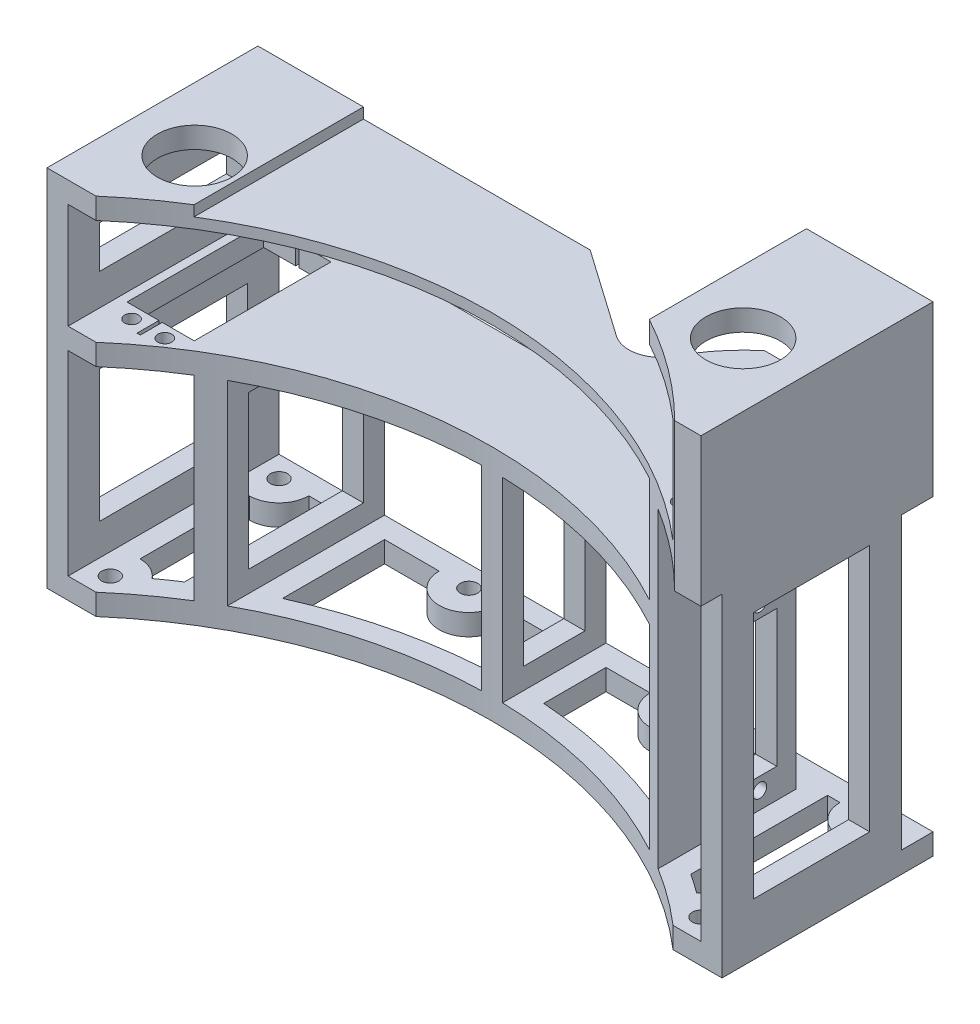
SolidWorks part; units mm, degrees
ref_plane "Front Plane" through (0, 0, 0) normal (0, 0, 1) x (1, 0, 0)
ref_plane "Top Plane" through (0, 0, 0) normal (0, 1, 0) x (1, 0, 0)
ref_plane "Right Plane" through (0, 0, 0) normal (1, 0, 0) x (0, 0, -1)
sketch "Sketch1" plane through (0, 0, 0) normal (0, 0, 1) x (1, 0, 0)
  line L0 (-101.6, 106.425) -> (101.6, 106.425)
  line L1 (-101.6, 0) -> (101.6, 0)
  line L2 (-101.6, 0) -> (-101.6, 106.425)
  line L4 (101.6, 0) -> (101.6, 106.425)
  point P5 (0, 0)
  dimension "D1" = 203.2
  dimension "D2" = 106.425
extrude "Boss-Extrude1" add sketch "Sketch1" along normal mid plane 63.5 contours L1 L4 L0 L2 | L0 region at (0, 53.2125, 0)
sketch "Sketch4" plane through (0, 0, -31.75) normal (0, 0, -1) x (-1, 0, 0)
  line L0 (-101.6, 0) -> (-101.6, 106.425) construction
  line L1 (101.6, 0) -> (101.6, 106.425) construction
  line L2 (-95.25, 103.25) -> (95.25, 103.25)
  line L3 (-95.25, 103.25) -> (-95.25, 71.5)
  line L4 (-95.25, 71.5) -> (95.25, 71.5)
  line L5 (95.25, 103.25) -> (95.25, 71.5)
  line L11 (-95.25, 65.15) -> (95.25, 65.15)
  line L12 (-95.25, 65.15) -> (-95.25, 6.35)
  line L13 (-95.25, 6.35) -> (95.25, 6.35)
  line L14 (95.25, 65.15) -> (95.25, 6.35)
  line L15 (101.6, 0) -> (-101.6, 0) construction
  dimension "D4" = 6.35
  dimension "D1" = 6.35
  dimension "D2" = 71.5
  dimension "D3" = 6.35
  dimension "D5" = 6.35
  dimension "D6" = 31.75
extrude "Cut-Extrude2" cut sketch "Sketch4" against normal through all
sketch "Sketch8" plane through (0, 0, 0) normal (0, 0, 1) x (1, 0, 0)
  line L0 (-95.25, 65.15) -> (95.25, 65.15) construction
  line L1 (-69.85, 65.15) -> (-63.5, 65.15)
  line L2 (-69.85, 65.15) -> (-69.85, 6.35)
  line L3 (-69.85, 6.35) -> (-63.5, 6.35)
  line L4 (-63.5, 65.15) -> (-63.5, 6.35)
  line L5 (95.25, 6.35) -> (-95.25, 6.35) construction
  line L6 (-95.25, 103.25) -> (95.25, 103.25) construction
  line L7 (63.5, 103.25) -> (69.85, 103.25)
  line L8 (63.5, 103.25) -> (63.5, 6.35)
  line L9 (63.5, 6.35) -> (69.85, 6.35)
  line L10 (69.85, 103.25) -> (69.85, 6.35)
  line L11 (95.25, 65.15) -> (95.25, 6.35) construction
  line L12 (-95.25, 6.35) -> (-95.25, 65.15) construction
  line L13 (-101.6, 0) -> (101.6, 0) construction
  line L14 (-3.175, 65.15) -> (3.175, 65.15)
  line L15 (-3.175, 65.15) -> (-3.175, 6.35)
  line L16 (-3.175, 6.35) -> (3.175, 6.35)
  line L17 (3.175, 65.15) -> (3.175, 6.35)
  point P24 (0, 0)
  point P25 (0, 6.35)
  dimension "D1" = 6.35
  dimension "D2" = 6.35
  dimension "D3" = 25.4
  dimension "D4" = 25.4
  dimension "D5" = 6.35
extrude "Boss-Extrude2" add sketch "Sketch8" along normal up to surface (31.75 mm away) from surface up to face at (0, 87.375, 31.75) starting at face at (0, 87.375, -31.75)
sketch "Sketch15" plane through (0, 103.25, 0) normal (0, -1, 0) x (1, 0, 0)
  line L4 (69.85, 31.75) -> (69.85, -31.75)
  line L5 (69.85, -31.75) -> (95.25, -31.75)
  line L6 (95.25, -31.75) -> (95.25, 31.75)
  line L7 (95.25, 31.75) -> (69.85, 31.75)
  line L8 (69.85, 31.75) -> (69.85, -31.75)
  line L9 (69.85, -31.75) -> (95.25, -31.75)
  line L10 (95.25, -31.75) -> (95.25, 31.75)
  line L11 (95.25, 31.75) -> (69.85, 31.75)
  dimension "D1" = 0
extrude "Boss-Extrude4" add sketch "Sketch15" along normal blind 3.175
sketch "Sketch2" plane through (0, 71.5, 0) normal (0, 1, 0) x (1, 0, 0)
  line L0 (-92.677, 24.55) -> (-72.423, -16.604) construction
  line L29 (-92.677, 24.55) -> (-83.05, 24.55)
  line L30 (-92.677, 24.55) -> (-92.677, -16.604)
  line L31 (-92.677, -16.604) -> (-83.05, -16.604)
  line L34 (-72.423, 24.55) -> (-72.423, -16.604)
  line L58 (69.85, 31.75) -> (69.85, -31.75)
  line L59 (69.85, -31.75) -> (95.25, -31.75)
  line L60 (95.25, -31.75) -> (95.25, 31.75)
  line L61 (95.25, 31.75) -> (69.85, 31.75)
  line L62 (69.85, 31.75) -> (69.85, -31.75)
  line L63 (69.85, -31.75) -> (95.25, -31.75)
  line L64 (95.25, -31.75) -> (95.25, 31.75)
  line L65 (95.25, 31.75) -> (69.85, 31.75)
  line L78 (-72.423, 24.55) -> (-92.677, -16.604) construction
  line L79 (-87.55, 28.273) -> (-77.55, -20.327) construction
  line L80 (-87.55, -20.327) -> (-77.55, 28.273) construction
  line L81 (-82.05, -16.604) -> (-72.423, -16.604)
  line L82 (-82.05, -16.604) -> (-82.05, -23.208)
  line L83 (-82.05, -23.208) -> (-83.05, -23.208)
  line L84 (-83.05, -16.604) -> (-83.05, -23.208)
  line L85 (-82.55, 3.973) -> (-13.3966, 3.973) construction
  line L86 (-82.05, 31.154) -> (-83.05, 31.154)
  line L87 (-82.05, 24.55) -> (-82.05, 31.154)
  line L88 (-83.05, 24.55) -> (-83.05, 31.154)
  line L89 (-82.05, 24.55) -> (-72.423, 24.55)
  line L90 (-101.6, -31.75) -> (101.6, -31.75) construction
  line L91 (-101.6, -31.75) -> (-101.6, 31.75) construction
  circle A12 centre (-87.55, -20.327) radius 2.1
  circle A13 centre (-77.55, -20.327) radius 2.1
  circle A14 centre (-87.55, 28.273) radius 2.1
  circle A15 centre (-77.55, 28.273) radius 2.1
  point P8 (-82.55, -23.208)
  point P17 (-82.55, 3.973)
  point P18 (-82.55, 3.973)
  point P27 (-82.55, -6.35)
  dimension "D3" = 48.6
  dimension "D4" = 4.2
  dimension "D2" = 10
  dimension "D5" = 41.154
  dimension "D6" = 20.254
  dimension "D7" = 1
  dimension "D8" = 6.604
  dimension "D9" = 30.9
  dimension "D10" = 25.4
  dimension "D11" = 0
  dimension "D12" = 19.05
extrude "Cut-Extrude3" cut sketch "Sketch2" against normal up to next
sketch "Sketch9" plane through (0, 106.425, 0) normal (0, 1, 0) x (1, 0, 0)
  line L0 (72.423, 24.55) -> (92.677, -16.604) construction
  line L1 (72.423, 24.55) -> (82.05, 24.55)
  line L2 (72.423, 24.55) -> (72.423, -16.604)
  line L3 (72.423, -16.604) -> (82.05, -16.604)
  line L4 (92.677, 24.55) -> (92.677, -16.604)
  line L5 (92.677, 24.55) -> (72.423, -16.604) construction
  line L6 (77.55, 28.273) -> (87.55, -20.327) construction
  line L7 (77.55, -20.327) -> (87.55, 28.273) construction
  line L8 (83.05, -16.604) -> (92.677, -16.604)
  line L9 (83.05, -16.604) -> (83.05, -23.208)
  line L10 (83.05, -23.208) -> (82.05, -23.208)
  line L11 (82.05, -16.604) -> (82.05, -23.208)
  line L12 (82.55, 3.973) -> (164.4034, 3.973) construction
  line L13 (83.05, 31.154) -> (82.05, 31.154)
  line L14 (83.05, 24.55) -> (83.05, 31.154)
  line L15 (82.05, 24.55) -> (82.05, 31.154)
  line L16 (83.05, 24.55) -> (92.677, 24.55)
  line L17 (101.6, -31.75) -> (101.6, 31.75) construction
  line L19 (-101.6, -31.75) -> (101.6, -31.75) construction
  circle A0 centre (77.55, -20.327) radius 2.1
  circle A1 centre (87.55, -20.327) radius 2.1
  circle A2 centre (77.55, 28.273) radius 2.1
  circle A3 centre (87.55, 28.273) radius 2.1
  point P8 (82.55, -23.208)
  point P17 (82.55, 3.973)
  point P18 (82.55, 3.973)
  point P27 (82.55, -6.35)
  dimension "D3" = 4.2
  dimension "D1" = 10
  dimension "D2" = 48.6
  dimension "D4" = 41.154
  dimension "D5" = 20.254
  dimension "D6" = 1
  dimension "D7" = 6.604
  dimension "D8" = 30.9
  dimension "D9" = 19.05
  dimension "D10" = 25.4
extrude "Cut-Extrude4" cut sketch "Sketch9" against normal up to next
sketch "Sketch12" plane through (0, 0, 0) normal (0, 1, 0) x (1, 0, 0)
  line L0 (-63.5, -31.75) -> (-63.5, 31.75) construction
  line L1 (-69.85, -31.75) -> (-95.25, -31.75) construction
  line L2 (-95.25, -31.75) -> (-95.25, 31.75) construction
  line L3 (-101.6, 31.75) -> (101.6, 31.75) construction
  circle A0 centre (-88.9, 25.4) radius 2.6
  circle A1 centre (-88.9, -25.4) radius 2.6
  circle A2 centre (-31.75, 25.4) radius 2.6
  dimension "D1" = 5.2
  dimension "D2" = 6.35
  dimension "D3" = 6.35
  dimension "D4" = 6.35
  dimension "D5" = 31.75
extrude "Cut-Extrude7" cut sketch "Sketch12" along normal up to surface (6.35 mm away) and the other way through all up to face at (-33.3375, 6.35, 0)
mirror "Mirror1" about plane through (0, 0, 0) normal (1, 0, 0) of "Cut-Extrude7"
sketch "Sketch16" plane through (0, 106.425, 0) normal (0, 1, 0) x (1, 0, 0)
  line L2 (-69.85, 31.75) -> (-101.6, 31.75)
  line L3 (-101.6, 31.75) -> (-101.6, -31.75)
  line L12 (-101.6, -31.75) -> (-69.85, -31.75)
  line L13 (-69.85, 31.75) -> (-69.85, -31.75)
  dimension "D1" = 31.75
extrude "Boss-Extrude5" add sketch "Sketch16" along normal blind 3.175
sketch "Sketch17" plane through (0, 109.6, 0) normal (0, 1, 0) x (1, 0, 0)
  line L0 (-101.6, -31.75) -> (-69.85, -31.75) construction
  line L1 (-101.6, 31.75) -> (-101.6, -31.75) construction
  circle A0 centre (-82.55, -6.35) radius 11.2395
  dimension "D3" = 22.479
  dimension "D1" = 25.4
  dimension "D2" = 19.05
extrude "Cut-Extrude8" cut sketch "Sketch17" against normal up to next
sketch "Sketch18" plane through (0, 106.425, 0) normal (0, 1, 0) x (1, 0, 0)
  line L5 (101.6, -31.75) -> (101.6, 31.75) construction
  line L6 (-69.85, -31.75) -> (101.6, -31.75) construction
  line L14 (101.6, -31.75) -> (101.6, 31.75)
  line L15 (101.6, 31.75) -> (95.25, 31.75)
  line L16 (95.25, -31.75) -> (95.25, 31.75)
  line L22 (95.25, -31.75) -> (82.55, -31.75)
  line L23 (101.6, -31.75) -> (101.6, -38.1)
  line L24 (101.6, -38.1) -> (82.55, -38.1)
  line L25 (82.55, -31.75) -> (82.55, -38.1)
  point P4 (0, 0)
  point P5 (95.25, -31.75)
  point P6 (95.25, 30.5966)
  dimension "D4" = 6.35
  dimension "D5" = 19.05
extrude "Boss-Extrude6" add sketch "Sketch18" along normal blind 38.1 from surface starting at face at (87.55, 100.075, 18.227)
sketch "Sketch20" plane through (0, 138.175, 0) normal (0, 1, 0) x (1, 0, 0)
  line L1 (63.5, 31.75) -> (101.6, 31.75)
  line L2 (63.5, 31.75) -> (63.5, -38.1)
  line L3 (63.5, -38.1) -> (101.6, -38.1)
  line L4 (101.6, 31.75) -> (101.6, -38.1)
  line L6 (-69.85, -31.75) -> (82.55, -31.75) construction
  circle A0 centre (82.55, -6.35) radius 11.2395
  point P0 (0, 0)
  dimension "D2" = 19.05
  dimension "D1" = 22.479
  dimension "D4" = 38.1
  dimension "D3" = 25.4
extrude "Boss-Extrude7" add sketch "Sketch20" along normal blind 6.35
sketch "Sketch10" plane through (0, 106.425, 0) normal (0, 1, 0) x (1, 0, 0)
  circle A3 centre (0, -132.08) radius 131.1117 construction
  circle A4 centre (0, -132.08) radius 131.1117 construction
  circle A5 centre (0, -132.08) radius 132.6992
  dimension "D1" = 1.5875
extrude "Cut-Extrude5" cut sketch "Sketch10" against normal through all both and the other way through all
sketch "Sketch21" plane through (0, 106.425, 0) normal (0, 1, 0) x (1, 0, 0)
  line L5 (34.6759, 6.35) -> (-1.5991, 31.75)
  line L6 (-69.85, 31.75) -> (95.25, 31.75) construction
  line L7 (-1.5991, 31.75) -> (50.9018, 31.75)
  arc A1 (34.6759, 6.35) -> (50.9018, 31.75) centre (82.55, -6.35) cw
  point P5 (37.1206, 13.3829)
  dimension "D2" = 49.53
  dimension "D1" = 35
  dimension "D3" = 25.4
extrude "Cut-Extrude10" cut sketch "Sketch21" against normal up to surface (3.175 mm away) up to face at (-82.55, 103.25, 17.5895)
sketch "Sketch32" plane through (0, 6.35, 0) normal (0, 1, 0) x (1, 0, 0)
  line L8 (76.2, 25.4) -> (76.2, -15.769)
  line L9 (88.9, -25.1619) -> (88.9, 25.4)
  line L10 (88.9, 25.4) -> (76.2, 25.4)
  line L11 (76.2, 25.4) -> (76.2, -15.769)
  line L12 (88.9, -16.45) -> (88.9, 16.45)
  line L13 (79.95, 25.4) -> (76.2, 25.4)
  line L32 (-57.15, 25.4) -> (-57.15, -5.3181)
  line L33 (-9.525, 6.6426) -> (-9.525, 25.4)
  line L40 (-76.2, -15.769) -> (-76.2, 25.4)
  line L41 (-76.2, 25.4) -> (-88.9, 25.4)
  line L42 (-88.9, 25.4) -> (-88.9, -25.1619)
  line L43 (-76.2, -15.769) -> (-76.2, 25.4)
  line L44 (-76.2, 25.4) -> (-79.95, 25.4)
  line L45 (-88.9, 16.45) -> (-88.9, -16.45)
  line L48 (-9.525, 25.4) -> (-57.15, 25.4)
  line L49 (-57.15, 25.4) -> (-57.15, -5.3181)
  line L50 (-9.525, 6.6426) -> (-9.525, 25.4)
  line L67 (-9.525, 25.4) -> (-22.8, 25.4)
  line L68 (-40.7, 25.4) -> (-57.15, 25.4)
  line L69 (22.8, 25.4) -> (9.525, 25.4)
  line L71 (9.525, 25.4) -> (9.525, 6.6426)
  line L72 (57.15, -5.3181) -> (57.15, 25.4)
  line L73 (57.15, 25.4) -> (9.525, 25.4)
  line L74 (9.525, 25.4) -> (9.525, 6.6426)
  line L75 (57.15, -5.3181) -> (57.15, 25.4)
  line L76 (57.15, 25.4) -> (40.7, 25.4)
  circle A2 centre (88.9, 25.4) radius 8.95
  arc A3 (79.95, 25.4) -> (88.9, 16.45) centre (88.9, 25.4) ccw
  arc A8 (88.9, -25.1619) -> (76.2, -15.769) centre (0, -132.08) ccw
  circle A9 centre (88.9, -25.4) radius 8.95
  arc A10 (88.9, -16.45) -> (81.9575, -19.7516) centre (88.9, -25.4) ccw
  arc A11 (81.9575, -19.7516) -> (76.2, -15.769) centre (0, -132.08) ccw
  circle A13 centre (-31.75, 25.4) radius 8.95
  arc A22 (-76.2, -15.769) -> (-88.9, -25.1619) centre (0, -132.08) ccw
  arc A23 (-76.2, -15.769) -> (-81.9575, -19.7516) centre (0, -132.08) ccw
  arc A26 (-40.7, 25.4) -> (-22.8, 25.4) centre (-31.75, 25.4) ccw
  circle A27 centre (-88.9, 25.4) radius 8.95
  arc A28 (-88.9, 16.45) -> (-79.95, 25.4) centre (-88.9, 25.4) ccw
  circle A30 centre (-88.9, -25.4) radius 8.95
  arc A31 (-81.9575, -19.7516) -> (-88.9, -16.45) centre (-88.9, -25.4) ccw
  circle A33 centre (31.75, 25.4) radius 8.95
  arc A35 (22.8, 25.4) -> (40.7, 25.4) centre (31.75, 25.4) ccw
  arc A38 (-9.525, 6.6426) -> (-57.15, -5.3181) centre (0, -132.08) ccw
  arc A39 (-9.525, 6.6426) -> (-57.15, -5.3181) centre (0, -132.08) ccw
  arc A42 (57.15, -5.3181) -> (9.525, 6.6426) centre (0, -132.08) ccw
  arc A43 (57.15, -5.3181) -> (9.525, 6.6426) centre (0, -132.08) ccw
  dimension "D1" = 6.35
  dimension "D2" = 6.35
  dimension "D3" = 6.35
  dimension "D4" = 6.35
  dimension "D5" = 6.35
  dimension "D6" = 6.35
  dimension "D7" = 6.35
  dimension "D8" = 6.35
  dimension "D9" = 6.35
  dimension "D10" = 6.35
extrude "Cut-Extrude19" cut sketch "Sketch32" against normal up to next
sketch "Sketch23" plane through (0, 0, -31.75) normal (0, 0, -1) x (-1, 0, 0)
  line L1 (-101.6, 6.35) -> (-57.15, 6.35)
  line L2 (-101.6, 6.35) -> (-101.6, 93.725)
  line L3 (-101.6, 93.725) -> (-57.15, 93.725)
  line L4 (-57.15, 6.35) -> (-57.15, 93.725)
  line L7 (-63.5, 71.5) -> (95.25, 71.5) construction
  line L9 (-63.5, 65.15) -> (-63.5, 6.35) construction
  line L10 (-101.6, 0) -> (-101.6, 144.525) construction
  line L11 (-63.5, 6.35) -> (-3.175, 6.35) construction
  dimension "D1" = 6.35
  dimension "D2" = 22.225
extrude "Cut-Extrude11" cut sketch "Sketch23" against normal blind 9.525
sketch "Sketch24" plane through (63.5, 0, 0) normal (-1, 0, 0) x (0, 0, 1)
  line L0 (-16.477, 56.354) -> (3.777, 15.2) construction
  line L1 (-16.477, 56.354) -> (-6.85, 56.354)
  line L2 (-16.477, 56.354) -> (-16.477, 15.2)
  line L3 (-16.477, 15.2) -> (-6.85, 15.2)
  line L4 (3.777, 56.354) -> (3.777, 15.2)
  line L5 (3.777, 56.354) -> (-16.477, 15.2) construction
  line L6 (-11.35, 60.077) -> (-1.35, 11.477) construction
  line L7 (-11.35, 11.477) -> (-1.35, 60.077) construction
  line L8 (-5.85, 15.2) -> (3.777, 15.2)
  line L9 (-5.85, 15.2) -> (-5.85, 8.596)
  line L10 (-5.85, 8.596) -> (-6.85, 8.596)
  line L11 (-6.85, 15.2) -> (-6.85, 8.596)
  line L12 (-6.35, 35.777) -> (65.4757, 35.777) construction
  line L13 (-5.85, 62.958) -> (-6.85, 62.958)
  line L14 (-5.85, 56.354) -> (-5.85, 62.958)
  line L15 (-6.85, 56.354) -> (-6.85, 62.958)
  line L16 (-5.85, 56.354) -> (3.777, 56.354)
  line L17 (-22.225, 65.15) -> (-22.225, 6.35) construction
  line L18 (15.5603, 65.15) -> (-22.225, 65.15) construction
  circle A0 centre (-11.35, 11.477) radius 2.1
  circle A1 centre (-1.35, 11.477) radius 2.1
  circle A2 centre (-11.35, 60.077) radius 2.1
  circle A3 centre (-1.35, 60.077) radius 2.1
  point P8 (-6.35, 8.596)
  point P17 (-6.35, 35.777)
  point P18 (-6.35, 35.777)
  point P27 (-6.35, 46.1)
  dimension "D3" = 4.2
  dimension "D1" = 10
  dimension "D2" = 48.6
  dimension "D4" = 41.154
  dimension "D5" = 20.254
  dimension "D6" = 1
  dimension "D7" = 6.604
  dimension "D8" = 30.9
  dimension "D9" = 15.875
  dimension "D10" = 19.05
extrude "Cut-Extrude12" cut sketch "Sketch24" against normal up to next
sketch "Sketch26" plane through (95.25, 0, 0) normal (-1, 0, 0) x (0, 0, 1)
  line L12 (-12.7, 90.55) -> (-12.7, 15.875)
  line L13 (-12.7, 15.875) -> (22.225, 15.875)
  line L14 (22.225, 15.875) -> (22.225, 90.55)
  line L15 (22.225, 90.55) -> (-12.7, 90.55)
  line L16 (-12.7, 90.55) -> (-12.7, 15.875)
  line L17 (-12.7, 15.875) -> (22.225, 15.875)
  line L18 (22.225, 15.875) -> (22.225, 90.55)
  line L19 (22.225, 90.55) -> (-12.7, 90.55)
  dimension "D1" = 9.525
extrude "Cut-Extrude13" cut sketch "Sketch26" against normal up to next
sketch "Sketch27" plane through (63.5, 0, 0) normal (-1, 0, 0) x (0, 0, 1)
  line L12 (-15.875, 96.9) -> (-15.875, 77.85)
  line L13 (-15.875, 77.85) -> (9.2103, 77.85)
  line L14 (9.2103, 77.85) -> (9.2103, 96.9)
  line L15 (9.2103, 96.9) -> (-15.875, 96.9)
  line L16 (-15.875, 96.9) -> (-15.875, 77.85)
  line L17 (-15.875, 77.85) -> (9.2103, 77.85)
  line L18 (9.2103, 77.85) -> (9.2103, 96.9)
  line L19 (9.2103, 96.9) -> (-15.875, 96.9)
  dimension "D1" = 6.35
extrude "Cut-Extrude14" cut sketch "Sketch27" against normal up to next
sketch "Sketch28" plane through (3.175, 0, 0) normal (1, 0, 0) x (0, 0, -1)
  line L8 (25.4, 58.8) -> (6.9313, 58.8)
  line L9 (6.9313, 58.8) -> (6.9313, 12.7)
  line L10 (6.9313, 12.7) -> (25.4, 12.7)
  line L11 (25.4, 12.7) -> (25.4, 58.8)
  line L12 (25.4, 58.8) -> (6.9313, 58.8)
  line L13 (6.9313, 58.8) -> (6.9313, 12.7)
  line L14 (6.9313, 12.7) -> (25.4, 12.7)
  line L15 (25.4, 12.7) -> (25.4, 58.8)
  dimension "D1" = 6.35
extrude "Cut-Extrude15" cut sketch "Sketch28" against normal up to next
sketch "Sketch29" plane through (-63.5, 0, 0) normal (1, 0, 0) x (0, 0, -1)
  line L8 (25.4, 58.8) -> (-9.2103, 58.8)
  line L9 (-9.2103, 58.8) -> (-9.2103, 12.7)
  line L10 (-9.2103, 12.7) -> (25.4, 12.7)
  line L11 (25.4, 12.7) -> (25.4, 58.8)
  line L12 (25.4, 58.8) -> (-9.2103, 58.8)
  line L13 (-9.2103, 58.8) -> (-9.2103, 12.7)
  line L14 (-9.2103, 12.7) -> (25.4, 12.7)
  line L15 (25.4, 12.7) -> (25.4, 58.8)
  dimension "D1" = 6.35
extrude "Cut-Extrude16" cut sketch "Sketch29" against normal up to next
sketch "Sketch30" plane through (-95.25, 0, 0) normal (1, 0, 0) x (0, 0, -1)
  line L8 (22.225, 15.875) -> (22.225, 55.625)
  line L9 (22.225, 55.625) -> (-22.225, 55.625)
  line L10 (-22.225, 55.625) -> (-22.225, 15.875)
  line L11 (-22.225, 15.875) -> (22.225, 15.875)
  line L12 (22.225, 15.875) -> (22.225, 55.625)
  line L13 (22.225, 55.625) -> (-22.225, 55.625)
  line L14 (-22.225, 55.625) -> (-22.225, 15.875)
  line L15 (-22.225, 15.875) -> (22.225, 15.875)
  dimension "D1" = 9.525
extrude "Cut-Extrude17" cut sketch "Sketch30" against normal up to next
sketch "Sketch31" plane through (-95.25, 0, 0) normal (1, 0, 0) x (0, 0, -1)
  line L8 (22.225, 81.025) -> (22.225, 93.725)
  line L9 (22.225, 93.725) -> (-22.225, 93.725)
  line L10 (-22.225, 93.725) -> (-22.225, 81.025)
  line L11 (-22.225, 81.025) -> (22.225, 81.025)
  line L12 (22.225, 81.025) -> (22.225, 93.725)
  line L13 (22.225, 93.725) -> (-22.225, 93.725)
  line L14 (-22.225, 93.725) -> (-22.225, 81.025)
  line L15 (-22.225, 81.025) -> (22.225, 81.025)
  dimension "D1" = 9.525
extrude "Cut-Extrude18" cut sketch "Sketch31" against normal up to next
fillet "Fillet1" radius 9.525 1 edges at (34.6759, 104.8375, -6.35)
equation "\"tightTol\"= 0.005in"
equation "\"normTol\"= 0.01in"
equation "\"looseTol\"= 0.02in"
equation "\"D1@Sketch12\"=5.2mm"
equation "\"D2@Sketch1\"=8mm+0.5+3.25+0.125"
equation "\"D2@Sketch4\"=8mm+0.25+2.25"
equation "\"D3@Sketch17\" = 7 / 8 + \"normTol\""
equation "\"D1@Sketch20\"=7/8+\"normTol\""
